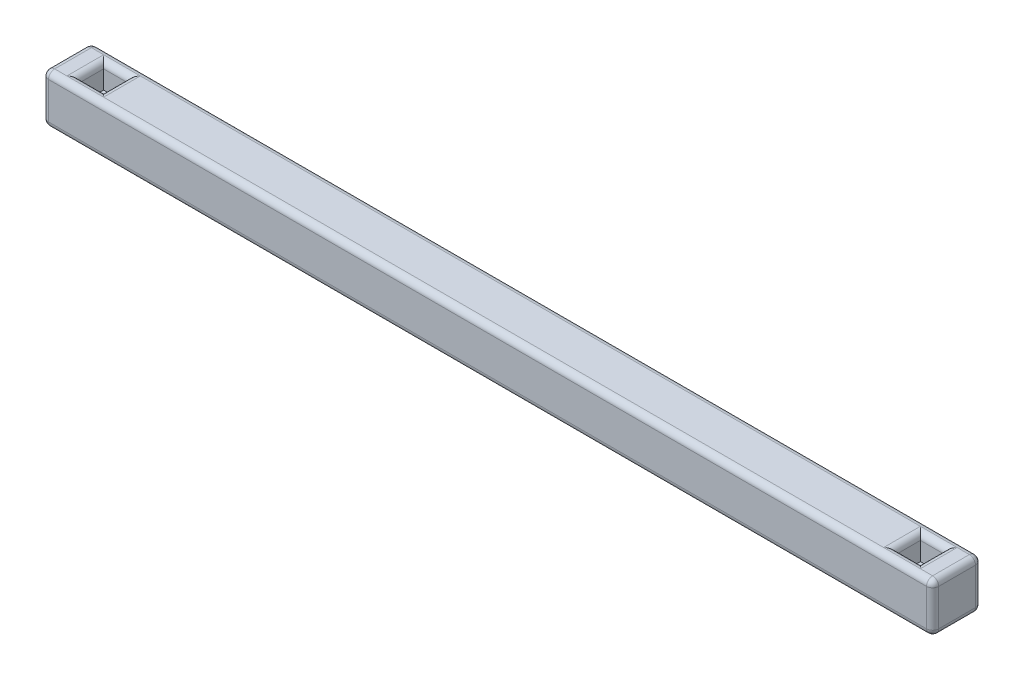
SolidWorks part; units mm, degrees
ref_plane "Front Plane" through (0, 0, 0) normal (0, 0, 1) x (1, 0, 0)
ref_plane "Top Plane" through (0, 0, 0) normal (0, 1, 0) x (1, 0, 0)
ref_plane "Right Plane" through (0, 0, 0) normal (1, 0, 0) x (0, 0, -1)
sketch "Sketch1" plane through (0, 0, 0) normal (0, 1, 0) x (1, 0, 0)
  line L1 (0, 0) -> (230.8225, 0)
  line L2 (0, 0) -> (0, 12.7)
  line L3 (0, 12.7) -> (230.8225, 12.7)
  line L4 (230.8225, 0) -> (230.8225, 12.7)
  dimension "D1" = 230.8225
  dimension "D2" = 12.7
extrude "Boss-Extrude1" add sketch "Sketch1" along normal blind 12.7 contours L3 L4 L1 L2
sketch "Sketch2" plane through (0, 12.7, 0) normal (0, 1, 0) x (1, 0, 0)
  line L0 (230.8225, 0) -> (230.8225, 12.7) construction
  line L1 (218.1225, 9.525) -> (224.4725, 9.525)
  line L2 (218.1225, 9.525) -> (218.1225, 3.175)
  line L3 (218.1225, 3.175) -> (224.4725, 3.175)
  line L4 (224.4725, 9.525) -> (224.4725, 3.175)
  line L5 (221.2975, 9.525) -> (221.2975, 12.7) construction
  line L6 (0, 12.7) -> (230.8225, 12.7) construction
  line L7 (221.2975, 3.175) -> (221.2975, 0) construction
  line L8 (0, 0) -> (230.8225, 0) construction
  line L9 (115.4113, 12.7) -> (115.4113, 0) construction
  line L10 (12.7, 3.175) -> (6.35, 3.175)
  line L11 (6.35, 9.525) -> (6.35, 3.175)
  line L12 (12.7, 9.525) -> (6.35, 9.525)
  line L13 (12.7, 9.525) -> (12.7, 3.175)
  point P4 (221.2975, 9.525)
  point P8 (230.8225, 6.35)
  dimension "D1" = 6.35
  dimension "D2" = 6.35
extrude "Cut-Extrude1" cut sketch "Sketch2" against normal blind 6.35
fillet "Fillet1" radius 1.5875 20 edges at (230.8225, 0, -6.35) (0, 0, -6.35) (230.8225, 6.35, -12.7) (0, 6.35, -12.7) (115.4113, 0, -12.7) (115.4113, 12.7, -12.7) (230.8225, 12.7, -6.35) (0, 12.7, -6.35) (6.35, 12.7, -6.35) (9.525, 12.7, -3.175) (12.7, 12.7, -6.35) (9.525, 12.7, -9.525) (224.4725, 12.7, -6.35) (221.2975, 12.7, -9.525) (218.1225, 12.7, -6.35) (221.2975, 12.7, -3.175) (0, 6.35, 0) (115.4113, 12.7, 0) (230.8225, 6.35, 0) (115.4113, 0, 0)
